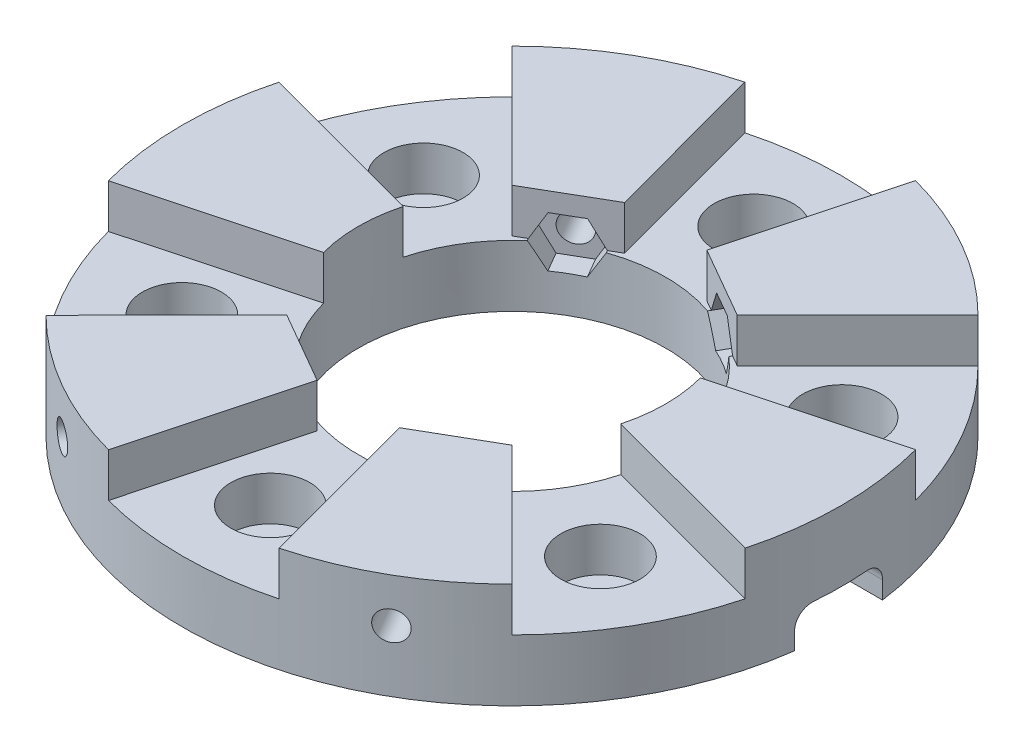
SolidWorks part; units mm, degrees
ref_plane "Front" through (0, 0, 0) normal (0, 0, 1) x (1, 0, 0)
ref_plane "Top" through (0, 0, 0) normal (0, 1, 0) x (1, 0, 0)
ref_plane "Right" through (0, 0, 0) normal (1, 0, 0) x (0, 0, -1)
sketch "Sketch1" plane through (0, 0, 0) normal (0, 1, 0) x (1, 0, 0)
  circle A0 centre (0, 0) radius 37.5
  circle A1 centre (0, 27.5) radius 2.3
  circle A2 centre (23.8157, 13.75) radius 2.3
  circle A3 centre (23.8157, -13.75) radius 2.3
  circle A4 centre (0, -27.5) radius 2.3
  circle A5 centre (-23.8157, -13.75) radius 2.3
  circle A6 centre (-23.8157, 13.75) radius 2.3
  point P17 (0, 0)
  dimension "D1" = 75
  dimension "D2" = 4.6
  dimension "D3" = 27.5
  dimension "D5" = 13.75
  dimension "D6" = 23.8157
  dimension "D7" = 23.8157
  dimension "D4" = 6
extrude "Boss-Extrude1" add sketch "Sketch1" along normal blind 2
sketch "Sketch2" plane through (0, 2, 0) normal (0, 1, 0) x (1, 0, 0)
  circle A0 centre (0, 0) radius 37.5
  circle A1 centre (0, -27.5) radius 2.3 construction
  circle A2 centre (0, -27.5) radius 2.3
  circle A3 centre (-23.8157, 13.75) radius 2.3 construction
  circle A4 centre (-23.8157, -13.75) radius 2.3 construction
  circle A5 centre (23.8157, -13.75) radius 2.3 construction
  circle A6 centre (23.8157, 13.75) radius 2.3 construction
  circle A7 centre (0, 27.5) radius 2.3 construction
  circle A8 centre (-23.8157, 13.75) radius 2.3
  circle A9 centre (-23.8157, -13.75) radius 2.3
  circle A10 centre (23.8157, -13.75) radius 2.3
  circle A11 centre (23.8157, 13.75) radius 2.3
  circle A12 centre (0, 27.5) radius 2.3
  circle A13 centre (0, 27.5) radius 4.5
  circle A14 centre (23.8157, 13.75) radius 4.5
  circle A15 centre (23.8157, -13.75) radius 4.5
  circle A16 centre (0, -27.5) radius 4.5
  circle A17 centre (-23.8157, -13.75) radius 4.5
  circle A18 centre (-23.8157, 13.75) radius 4.5
  point P34 (0, 0)
  circle M10 centre (0, 0) radius 37.5
  dimension "D1" = 9
  dimension "D3" = 75
  dimension "D2" = 6
extrude "Boss-Extrude2" add sketch "Sketch2" along normal blind 5 contours A18 A17 A16 A15 A14 A13 M10 region at (0, 2, 0)
sketch "Sketch3" plane through (0, 7, 0) normal (0, 1, 0) x (1, 0, 0)
  line L0 (-23.8157, 13.75) -> (-15.1554, 8.75)
  line L1 (-23.8157, 13.75) -> (-32.476, 18.75)
  line L2 (0, 0) -> (-36.2261, 9.6913)
  line L3 (0, 0) -> (-36.2184, -9.7201)
  line L4 (0, 0) -> (-9.7201, 36.2184)
  line L5 (0, 0) -> (-26.5271, 26.506)
  line L6 (0, 0) -> (26.506, 26.5271)
  line L7 (0, 0) -> (9.6913, 36.2261)
  line L8 (0, 0) -> (36.2261, -9.6913)
  line L9 (0, 0) -> (36.2184, 9.7201)
  line L10 (0, 0) -> (9.7201, -36.2184)
  line L11 (0, 0) -> (26.5271, -26.506)
  line L12 (0, 0) -> (-26.506, -26.5271)
  line L13 (0, 0) -> (-9.6913, -36.2261)
  line L14 (-12.8058, -12.816) -> (-4.6821, -17.5019)
  line L15 (-12.8058, -12.816) -> (-12.3694, -12.3793)
  line L16 (-4.6821, -17.5019) -> (-4.5226, -16.9055)
  line L17 (4.6947, -17.4931) -> (12.8197, -12.8095)
  line L18 (-4.6982, 17.5061) -> (-12.8102, 12.8)
  line L19 (4.6802, 17.4945) -> (12.8112, 12.8214)
  line L20 (0, 0) -> (0, 37.5)
  line L21 (-12.8102, 12.8) -> (-12.3677, 12.3579)
  line L22 (-4.6982, 17.5061) -> (-4.5361, 16.9019)
  line L23 (4.6802, 17.4945) -> (4.5216, 16.9019)
  line L24 (12.8112, 12.8214) -> (12.3776, 12.3875)
  circle A0 centre (0, 0) radius 37.5
  circle A1 centre (0, 0) radius 17.5
  point P22 (0, 0)
  circle M7 centre (0, 0) radius 37.5
  dimension "D1" = 75
  dimension "D2" = 6
  dimension "D5" = 30
extrude "Boss-Extrude3" add sketch "Sketch3" along normal blind 5 contours A1 L2 L3 M7 | A1 L4 L5 M7 | A1 L6 L7 M7 | A1 L8 L9 M7 | A1 L10 L11 M7 | A1 L12 L13 M7 region at (-28.3853, 7, 0.0113) region at (-14.2392, 7, -24.6396) region at (28.3853, 7, -0.0113) region at (-14.2192, 7, 24.6511) region at (14.2189, 7, -24.6513) region at (14.2386, 7, 24.6399)
sketch "Sketch4" plane through (0, 7, 0) normal (0, 1, 0) x (1, 0, 0)
  circle A0 centre (0, 0) radius 17.5
extrude "Cut-Extrude1" cut sketch "Sketch4" against normal blind 7
sketch "Sketch5" plane through (-8.744, 0, 15.1589) normal (0.4997, 0, -0.8662) x (-0.8662, 0, -0.4997)
  line L0 (4.6891, 12) -> (-4.6891, 12) construction
  line L1 (3.2909, 7) -> (1.6454, 9.85)
  line L2 (1.6454, 9.85) -> (-1.6454, 9.85)
  line L3 (-1.6454, 9.85) -> (-3.2909, 7)
  line L4 (-3.2909, 7) -> (-1.6454, 4.15)
  line L5 (-1.6454, 4.15) -> (1.6454, 4.15)
  line L6 (1.6454, 4.15) -> (3.2909, 7)
  line L7 (0, 7) -> (4.6891, 7)
  line L8 (4.6891, 12) -> (4.6891, 7) construction
  line L9 (0, 7) -> (-4.6891, 7)
  line L10 (-4.6891, 12) -> (-4.6891, 7) construction
  circle A0 centre (0, 7) radius 1.5
  circle A1 centre (0, 7) radius 2.85 construction
  point P2 (0, 12)
  line M2 (0, 7) -> (4.6891, 7)
  line M6 (-4.6891, 7) -> (0, 7)
  dimension "D1" = 3
  dimension "D3" = 5.7
  dimension "D2" = 5
extrude "Cut-Extrude2" cut sketch "Sketch5" against normal blind 2.5 and the other way blind 7 contours A0 L7 L1 L2 L3 M6 | A0 L4 L5 L6 L7 M6 | A0 L9 M2 | L9 A0 M2 region at (-10.819, 7.0717, 13.962) region at (-10.8282, 5.6109, 13.9567) region at (-8.744, 6.3634, 15.1589) region at (-8.744, 7.6366, 15.1589)
sketch "Sketch7" plane through (8.7396, 0, 15.1614) normal (-0.4994, 0, -0.8664) x (-0.8664, 0, 0.4994)
  line L0 (4.6688, 12) -> (-4.7094, 12) construction
  line L1 (3.2706, 7) -> (1.6252, 9.85)
  line L2 (1.6252, 9.85) -> (-1.6657, 9.85)
  line L3 (-1.6657, 9.85) -> (-3.3112, 7)
  line L4 (-3.3112, 7) -> (-1.6657, 4.15)
  line L5 (-1.6657, 4.15) -> (1.6252, 4.15)
  line L6 (1.6252, 4.15) -> (3.2706, 7)
  line L7 (-0.0203, 7) -> (4.6688, 7)
  line L8 (-0.0203, 7) -> (-4.7094, 7)
  line L9 (-4.7094, 12) -> (-4.7094, 7) construction
  line L10 (4.6688, 12) -> (4.6688, 7) construction
  circle A0 centre (-0.0203, 7) radius 2.85 construction
  line M7 (0, 7) -> (4.6688, 7)
  line M11 (-4.7094, 7) -> (0, 7)
  dimension "D1" = 5.7
  dimension "D2" = 5
extrude "Cut-Extrude4" cut sketch "Sketch7" against normal blind 2.5 and the other way blind 3 contours L2 L3 L1 M11 M7 | L5 L6 L4 M7 M11 region at (8.7572, 8.2667, 15.1513) region at (8.7572, 5.7333, 15.1513)
sketch "Sketch10" plane through (8.7396, 0, 15.1614) normal (-0.4994, 0, -0.8664) x (-0.8664, 0, 0.4994)
  line L0 (1.6252, 4.15) -> (3.2706, 7) construction
  line L1 (-1.6657, 4.15) -> (1.6252, 4.15) construction
  line L2 (4.6688, 12) -> (-4.7094, 12) construction
  circle A0 centre (-0.0203, 7) radius 1.65
  dimension "D1" = 3.3
  dimension "D2" = 2.85
  dimension "D3" = 2.85
  dimension "D4" = 5
extrude "Cut-Extrude7" cut sketch "Sketch10" against normal blind 20
sketch "Sketch9" plane through (-9.9931, 0, 17.3245) normal (0.4997, 0, -0.8662) x (-0.8662, 0, -0.4997)
  line L0 (-1.6454, 4.15) -> (1.6454, 4.15) construction
  circle A0 centre (0, 6.9) radius 1.65
  point P2 (0, 4.15)
  dimension "D1" = 3.3
  dimension "D2" = 2.75
extrude "Cut-Extrude6" cut sketch "Sketch9" against normal blind 20
sketch "Sketch14" plane through (0, 0, 0) normal (0, -1, 0) x (1, 0, 0)
  line L0 (37.1652, -5) -> (16.7705, -5)
  line L1 (37.1652, 5) -> (16.7705, 5)
  line L2 (0, 0) -> (0, -37.5)
  line L3 (0, 0) -> (37.5, 0)
  circle A2 centre (0, 0) radius 17.5
  circle A3 centre (0, 0) radius 37.5
  circle M1 centre (0, 0) radius 17.5
  circle M5 centre (0, 0) radius 37.5
  dimension "D2" = 75
  dimension "D3" = 35
  dimension "D1" = 90
  dimension "D4" = 5
  dimension "D5" = 5
extrude "Cut-Extrude8" cut sketch "Sketch14" against normal blind 4 contours L3 L1 M1 M5 | L3 L0 M1 M5 region at (27.3228, 0, -2.5081) region at (27.3228, 0, 2.5081)
sketch "Sketch15" plane through (-8.7815, 0, -15.1372) normal (0.5018, 0, 0.865) x (0.865, 0, -0.5018)
  line L1 (3.2909, 7) -> (1.6454, 9.85)
  line L2 (1.6454, 9.85) -> (-1.6454, 9.85)
  line L3 (-1.6454, 9.85) -> (-3.2909, 7)
  line L4 (-3.2909, 7) -> (-1.6454, 4.15)
  line L5 (-1.6454, 4.15) -> (1.6454, 4.15)
  line L6 (1.6454, 4.15) -> (3.2909, 7)
  circle A0 centre (0, 7) radius 2.85 construction
  circle A1 centre (0, 7) radius 1.5
  line M1 (0, 7) -> (4.7207, 7)
  line M5 (-4.6575, 7) -> (0, 7)
  dimension "D2" = 3
  dimension "D1" = 5.7
extrude "Cut-Extrude9" cut sketch "Sketch15" against normal blind 2.5 and the other way blind 10 contours A1 M1 M5 | A1 L4 L5 L6 M5 M1 | A1 L1 L2 L3 M1 M5 | A1 M5 M1 region at (-6.7095, 7.0717, -16.3392) region at (-6.7003, 5.6109, -16.3446) region at (-8.7815, 7.6366, -15.1372) region at (-8.7815, 6.3634, -15.1372)
sketch "Sketch16" plane through (-10.036, 0, -17.2997) normal (0.5018, 0, 0.865) x (0.865, 0, -0.5018)
  line L0 (-1.6454, 4.15) -> (1.6454, 4.15) construction
  line L1 (-1.6454, 9.85) -> (-3.2909, 7) construction
  circle A0 centre (0, 7) radius 1.65
  dimension "D2" = 3.3
  dimension "D1" = 2.85
  dimension "D3" = 2.85
extrude "Cut-Extrude10" cut sketch "Sketch16" against normal blind 20
sketch "Sketch17" plane through (8.72, 0, -15.1727) normal (-0.4983, 0, 0.867) x (0.867, 0, 0.4983)
  line L1 (3.2909, 7) -> (1.6454, 9.85)
  line L2 (1.6454, 9.85) -> (-1.6454, 9.85)
  line L3 (-1.6454, 9.85) -> (-3.2909, 7)
  line L4 (-3.2909, 7) -> (-1.6454, 4.15)
  line L5 (-1.6454, 4.15) -> (1.6454, 4.15)
  line L6 (1.6454, 4.15) -> (3.2909, 7)
  circle A0 centre (0, 7) radius 2.85 construction
  dimension "D1" = 5.7
extrude "Cut-Extrude11" cut sketch "Sketch17" against normal blind 2.5 and the other way blind 10
sketch "Sketch18" plane through (9.9657, 0, -17.3403) normal (-0.4983, 0, 0.867) x (0.867, 0, 0.4983)
  line L0 (-1.6454, 9.85) -> (-3.2909, 7) construction
  line L1 (-1.6454, 4.15) -> (1.6454, 4.15) construction
  circle A0 centre (0, 7) radius 1.65
  dimension "D1" = 3.3
  dimension "D2" = 2.85
  dimension "D3" = 2.85
extrude "Cut-Extrude12" cut sketch "Sketch18" against normal blind 20
fillet "Fillet1" radius 2 2 edges at (26.9678, 4, -5) (26.9678, 4, 5)
